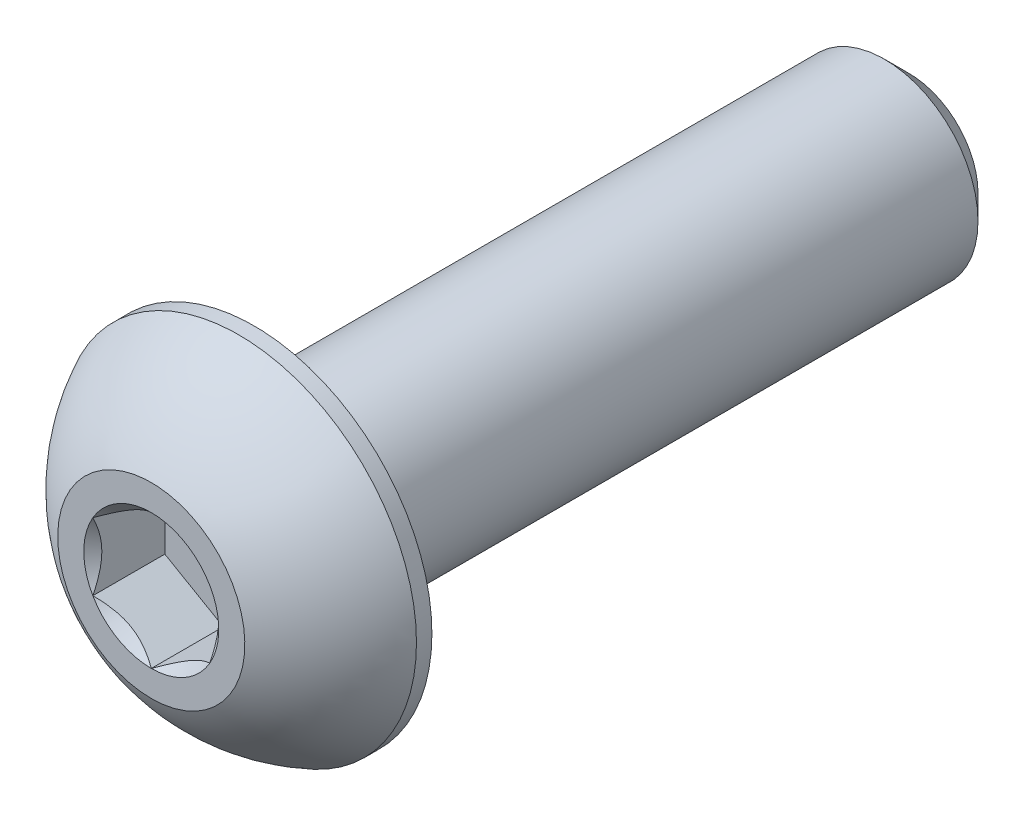
SolidWorks part; units mm, degrees
ref_plane "Front" through (0, 0, 0) normal (0, 0, 1) x (1, 0, 0)
ref_plane "Top" through (0, 0, 0) normal (0, 1, 0) x (1, 0, 0)
ref_plane "Right" through (0, 0, 0) normal (1, 0, 0) x (0, 0, -1)
sketch "Sketch1" plane through (0, 0, 0) normal (1, 0, 0) x (0, 0, -1)
  line L2 (2.2, 2) -> (16.2, 2)
  line L3 (16.2, 2) -> (16.2, 0)
  line L4 (16.2, 0) -> (2.2, 0)
  line L6 (1.87, 3.8) -> (2.2, 3.8) construction
  line L7 (16.2, 2) -> (16.2, -2) construction
  line L8 (0, 0) -> (2.2, 0) construction
  line L9 (2.2, 3.8) -> (2.2, -3.8) construction
  line L11 (2.2, 2) -> (2.2, 0)
  line L13 (0, 1.25) -> (0, -1.25) construction
  line L14 (0, 1.25) -> (0, 2) construction
  line L15 (16.1562, 2.0758) -> (16.5062, 1.4696) construction
  line L16 (16.5062, 1.4696) -> (16.8562, 2.0758) construction
  line L17 (16.8562, 2.0758) -> (16.1562, 2.0758) construction
  line L18 (16.2, 2) -> (16.8125, 2) construction
  line L19 (16.5062, 2.0758) -> (16.5062, 2) construction
  line L20 (16.5062, 2) -> (16.5062, 1.5453) construction
  line L21 (16.5062, 1.5453) -> (16.5062, 1.4696) construction
  line L22 (16.4625, 1.5453) -> (16.55, 1.5453)
  line L23 (16.1781, 2.0379) -> (16.8344, 2.0379)
  line L24 (16.55, 1.5453) -> (16.8344, 2.0379)
  line L25 (16.4625, 1.5453) -> (16.1781, 2.0379)
  line L26 (15.675, 2) -> (16.2, 1.475)
  arc A3 (0, 2) -> (1.87, 3.8) centre (3.7264, 0) cw construction
  point P29 (16.5062, 2.0379)
  point P30 (14.45, -2)
  dimension "D1" = 0.33
  dimension "Pitch" = 0.7
  dimension "D3" = 0.0875
  dimension "D2" = 0.525
  dimension "D4" = 45
  dimension "D5" = 1.75
sketch "Sketch10" plane through (0, 0, 0) normal (1, 0, 0) x (0, 0, -1)
  line L0 (15.675, 2) -> (16.2, 1.475) construction
  line L1 (15.675, 2) -> (16.2, 1.475)
  line L4 (16.2, 2) -> (2.2, 2)
  line L5 (16.2, 0) -> (16.2, 2)
  line L6 (2.2, 0) -> (16.2, 0)
  line L7 (2.2, 2) -> (2.2, 0)
  line L8 (15.675, 2) -> (2.2, 2)
  line L9 (16.2, 0) -> (16.2, 1.475)
  line L10 (2.2, 0) -> (16.2, 0)
  line L11 (2.2, 2) -> (2.2, 0)
  dimension "D1" = 0
revolve "Revolve3" add sketch "Sketch10" angle 360 about L8
sketch "Sketch7" plane through (0, 0, 0) normal (1, 0, 0) x (0, 0, -1)
  line L6 (1.87, 3.8) -> (2.2, 3.8) construction
  line L8 (0, 0) -> (2.2, 0) construction
  line L11 (2.2, 3.8) -> (2.2, -3.8) construction
  line L12 (1.87, 3.8) -> (2.2, 3.8)
  line L13 (0, 0) -> (2.2, 0)
  line L14 (0, 1.25) -> (0, -1.25) construction
  line L15 (2.2, 3.8) -> (2.2, 0)
  line L16 (0, 2) -> (0, 0)
  arc A2 (1.87, 3.8) -> (0, 2) centre (3.7264, 0) ccw construction
  arc A3 (1.87, 3.8) -> (0, 2) centre (3.7264, 0) ccw
revolve "Revolve2" add sketch "Sketch7" angle 360 mid plane about L13
sketch "Sketch5" plane through (0, 0, 0) normal (0, 0, 1) x (1, 0, 0)
  line L1 (1.25, -0.7217) -> (1.25, 0.7217)
  line L2 (1.25, 0.7217) -> (0, 1.4434)
  line L3 (0, 1.4434) -> (-1.25, 0.7217)
  line L4 (-1.25, 0.7217) -> (-1.25, -0.7217)
  line L5 (-1.25, -0.7217) -> (0, -1.4434)
  line L6 (0, -1.4434) -> (1.25, -0.7217)
  circle A0 centre (0, 0) radius 1.25 construction
extrude "Cut-Extrude2" cut sketch "Sketch5" against normal blind 1.54
sketch "Sketch6" plane through (0, 0, 0) normal (0, 0, 1) x (1, 0, 0)
  circle A0 centre (0, 0) radius 1.4434
extrude "Cut-Extrude3" cut sketch "Sketch6" against normal blind 1.54 draft 45
sketch "Sketch9" [suppressed] plane through (0, 0, -2.2) normal (0, 0, -1) x (-1, 0, 0)
  circle A0 centre (0, 0) radius 2 construction
  circle A4 centre (0, 0) radius 2
split "Split1" [suppressed] bodies to split 113
sketch "Sketch11" [suppressed] plane through (0, 0, -16.2) normal (0, 0, -1) x (-1, 0, 0)
  circle A0 centre (0, 0) radius 2 construction
  circle A1 centre (0, 0) radius 2
curve "Helix/Spiral1" [suppressed] pitch 0.7 height 16.2 turns 23.1429
sketch "Sketch12" [suppressed] plane through (0, 0, 0) normal (1, 0, 0) x (0, 0, -1)
  line L0 (16.4625, 1.5453) -> (16.55, 1.5453) construction
  line L1 (16.55, 1.5453) -> (16.8344, 2.0379) construction
  line L2 (16.1781, 2.0379) -> (16.8344, 2.0379) construction
  line L3 (16.4625, 1.5453) -> (16.1781, 2.0379) construction
  line L4 (16.4625, 1.5453) -> (16.55, 1.5453)
  line L5 (16.55, 1.5453) -> (16.8344, 2.0379)
  line L6 (16.1781, 2.0379) -> (16.8344, 2.0379)
  line L7 (16.4625, 1.5453) -> (16.1781, 2.0379)
sweep "Cut-Sweep2" [suppressed] cut profiles "Sketch12" path "Helix/Spiral1"
extrude "Boss-Extrude1" [suppressed] add sketch "Sketch9" along normal blind 10 draft 45
equation "\"D1@Cut-Extrude2\" = \"Head Ht@Sketch1\" * .7"
equation "\"D1@Sketch1\" = \"Head Ht@Sketch1\" * .15"
equation "\"D1@Cut-Extrude3\" = \"D1@Cut-Extrude2\""
equation "\"D3@Sketch1\" = \"Pitch@Sketch1\" / 8"
equation "\"D2@Sketch1\"=\"Pitch@Sketch1\"*0.75"
equation "\"D3@Helix/Spiral1\" = \"Lg@Sketch1\" + \"Head Ht@Sketch1\""
equation "\"D4@Helix/Spiral1\"=\"pitch@sketch1\""
equation "\"D5@Sketch1\"=\"Pitch@Sketch1\"*2.5"
